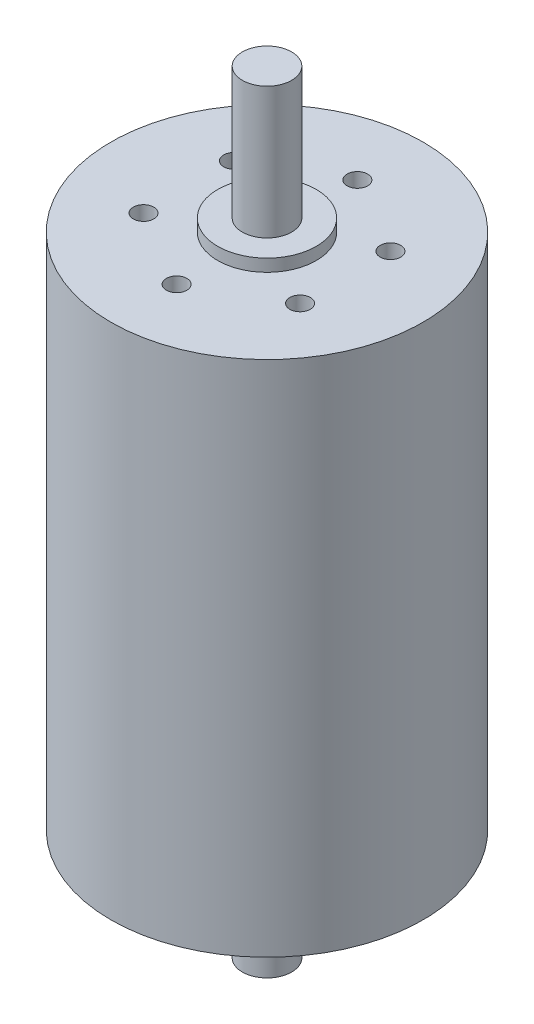
SolidWorks part; units mm, degrees
ref_plane "Face" through (0, 0, 0) normal (0, 0, 1) x (1, 0, 0)
ref_plane "Dessus" through (0, 0, 0) normal (0, 1, 0) x (1, 0, 0)
ref_plane "Droite" through (0, 0, 0) normal (1, 0, 0) x (0, 0, -1)
sketch "Esquisse1" plane through (0, 0, 0) normal (0, 0, 1) x (1, 0, 0)
  line L0 (0, 0) -> (0, 94)
  line L1 (0, 94) -> (3, 94)
  line L2 (3, 94) -> (3, 78)
  line L3 (3, 78) -> (6, 78)
  line L4 (6, 78) -> (6, 76.5)
  line L5 (6, 76.5) -> (19, 76.5)
  line L6 (19, 76.5) -> (19, 13.5)
  line L7 (19, 13.5) -> (6, 13.5)
  line L8 (6, 13.5) -> (6, 12)
  line L9 (6, 12) -> (3, 12)
  line L10 (3, 12) -> (3, 0)
  line L11 (3, 0) -> (0, 0)
  dimension "D1" = 19
  dimension "D2" = 63
  dimension "D3" = 3
  dimension "D4" = 6
  dimension "D5" = 1.5
  dimension "D6" = 12
  dimension "D7" = 16
revolve "Révolution1" add sketch "Esquisse1" angle 360 about L0
sketch "Esquisse2" plane through (0, 76.5, 0) normal (0, 1, 0) x (1, 0, 0)
  line L0 (0, 0) -> (0, 11) construction
  circle A0 centre (0, 11) radius 1.25
  circle A1 centre (9.5263, 5.5) radius 1.25
  circle A2 centre (9.5263, -5.5) radius 1.25
  circle A3 centre (0, -11) radius 1.25
  circle A4 centre (-9.5263, -5.5) radius 1.25
  circle A5 centre (-9.5263, 5.5) radius 1.25
  point P4 (-12.2758, 7.3655)
  point P5 (0, 0)
  point P17 (0, 0)
  dimension "D1" = 2.5
  dimension "D2" = 11
  dimension "D3" = 6
extrude "Enlèv. mat.-Extru.1" cut sketch "Esquisse2" against normal blind 5
extrude "Enlèv. mat.-Extru.2" cut sketch "Esquisse2<2>" along normal blind 5 from surface starting at face at (0, 13.5, -19)
sketch "Esquisse2<2>" plane through (0, 76.5, 0) normal (0, 1, 0) x (1, 0, 0) same geometry as "Esquisse2"
